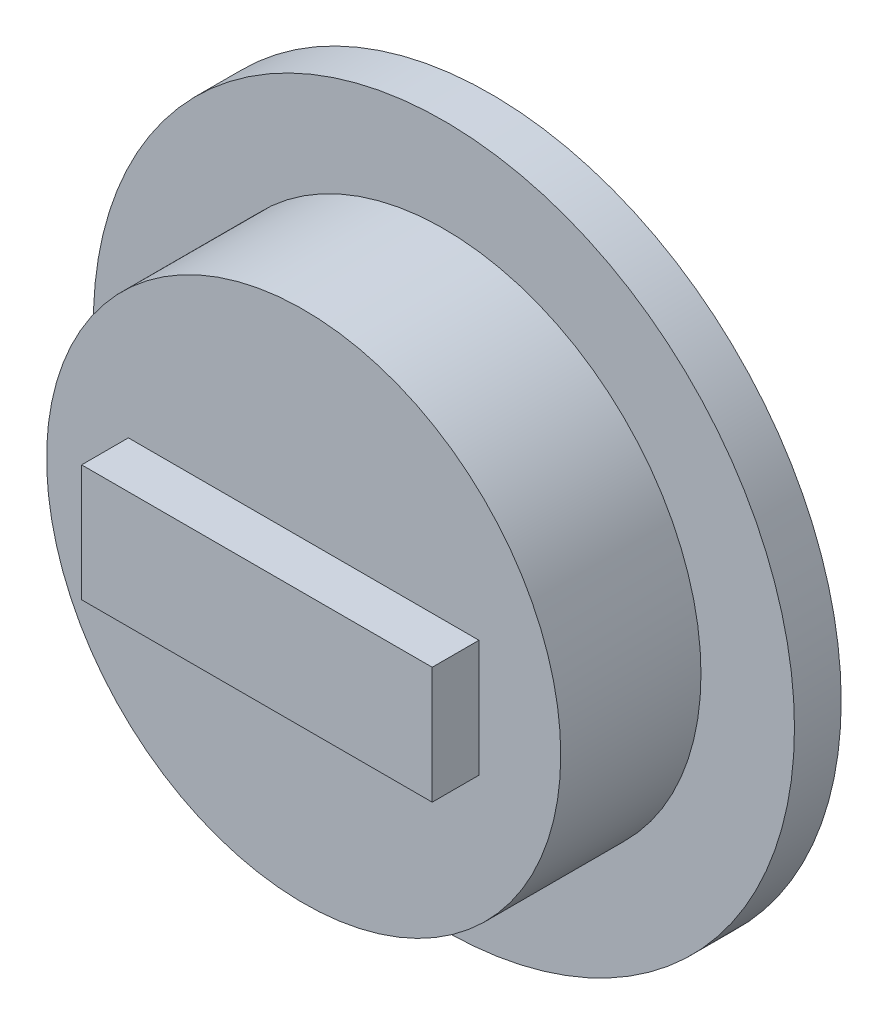
SolidWorks part; units mm, degrees
ref_plane "Спереди" through (0, 0, 0) normal (0, 0, 1) x (1, 0, 0)
ref_plane "Сверху" through (0, 0, 0) normal (0, 1, 0) x (1, 0, 0)
ref_plane "Справа" through (0, 0, 0) normal (1, 0, 0) x (0, 0, -1)
sketch "Эскиз1" plane through (0, 0, 0) normal (0, 0, 1) x (1, 0, 0)
  circle A0 centre (0, 0) radius 15
  dimension "D1" = 30
extrude "Бобышка-Вытянуть1" add sketch "Эскиз1" along normal blind 2
sketch "Эскиз2" plane through (0, 0, 0) normal (0, 0, 1) x (1, 0, 0)
  circle A0 centre (0, 0) radius 11
  dimension "D1" = 22
extrude "Бобышка-Вытянуть2" add sketch "Эскиз2" along normal blind 6 from offset 2
sketch "Эскиз3" plane through (0, 0, 0) normal (0, 0, 1) x (1, 0, 0)
  line L1 (-7.5, -2.5) -> (7.5, -2.5)
  line L2 (-7.5, -2.5) -> (-7.5, 2.5)
  line L3 (-7.5, 2.5) -> (7.5, 2.5)
  line L4 (7.5, -2.5) -> (7.5, 2.5)
  line L5 (-7.5, -2.5) -> (7.5, 2.5) construction
  line L6 (-7.5, 2.5) -> (7.5, -2.5) construction
  point P0 (0, 0)
  dimension "D1" = 5
  dimension "D2" = 15
extrude "Бобышка-Вытянуть3" add sketch "Эскиз3" along normal blind 10
sketch "Эскиз4" plane through (0, 0, 0) normal (0, 0, 1) x (1, 0, 0)
  line L1 (-7.5, 2) -> (7.5, 2)
  line L2 (-7.5, 2) -> (-7.5, 6)
  line L3 (-7.5, 6) -> (7.5, 6)
  line L4 (7.5, 2) -> (7.5, 6)
  line L5 (-7.5, -6) -> (7.5, -6)
  line L6 (-7.5, -6) -> (-7.5, -2)
  line L7 (-7.5, -2) -> (7.5, -2)
  line L8 (7.5, -6) -> (7.5, -2)
  dimension "D1" = 15
  dimension "D2" = 7.5
  dimension "D3" = 2
  dimension "D4" = 4
  dimension "D5" = 4
  dimension "D6" = 7.5
  dimension "D7" = 15
  dimension "D8" = 2
extrude "Вырез-Вытянуть1" cut sketch "Эскиз4" along normal blind 4
